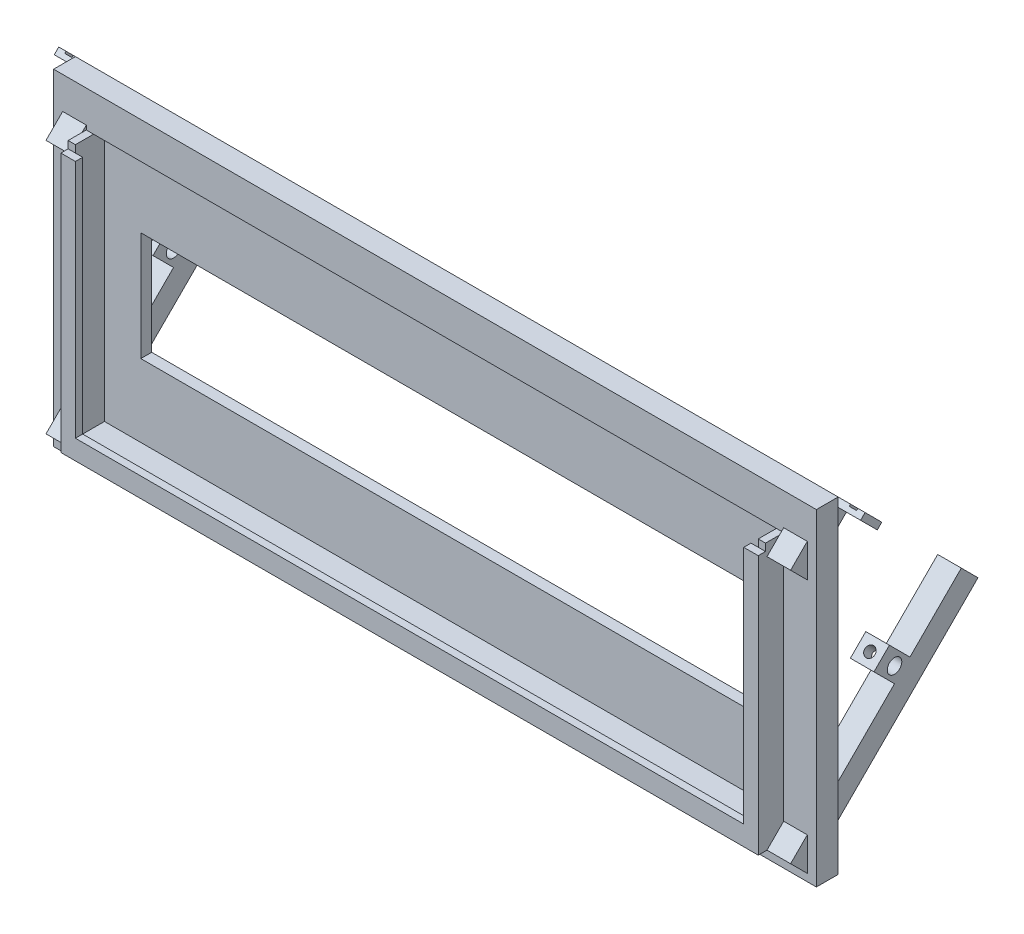
SolidWorks part; units mm, degrees
ref_plane "Front Plane" through (0, 0, 0) normal (0, 0, 1) x (1, 0, 0)
ref_plane "Top Plane" through (0, 0, 0) normal (0, 1, 0) x (1, 0, 0)
ref_plane "Right Plane" through (0, 0, 0) normal (1, 0, 0) x (0, 0, -1)
sketch "Sketch2" plane through (0, 0, 0) normal (0, 0, 1) x (1, 0, 0)
  line L1 (-105, 45) -> (105, 45)
  line L2 (-105, 45) -> (-105, -45)
  line L3 (-105, -45) -> (105, -45)
  line L4 (105, 45) -> (105, -45)
  line L5 (-105, 45) -> (105, -45) construction
  line L6 (-105, -45) -> (105, 45) construction
  point P0 (0, 0)
  dimension "D1" = 210
  dimension "D2" = 90
extrude "Boss-Extrude1" add sketch "Sketch2" along normal blind 6
sketch "Sketch3" plane through (0, 0, 6) normal (0, 0, 1) x (1, 0, 0)
  line L1 (-94, 35) -> (94, 35)
  line L2 (-94, 35) -> (-94, -35)
  line L3 (-94, -35) -> (94, -35)
  line L4 (94, 35) -> (94, -35)
  line L5 (-94, 35) -> (94, -35) construction
  line L6 (-94, -35) -> (94, 35) construction
  point P0 (0, 0)
  dimension "D1" = 70
  dimension "D2" = 188
extrude "Cut-Extrude1" cut sketch "Sketch3" against normal blind 3
sketch "Sketch4" plane through (0, 0, 3) normal (0, 0, 1) x (1, 0, 0)
  line L0 (94, -35) -> (94, 35) construction
  line L1 (-84, -15) -> (84, -15)
  line L2 (-84, -15) -> (-84, 15)
  line L3 (-84, 15) -> (84, 15)
  line L4 (84, -15) -> (84, 15)
  line L5 (-84, -15) -> (84, 15) construction
  line L6 (-84, 15) -> (84, -15) construction
  line L7 (-94, -35) -> (94, -35) construction
  point P0 (0, 0)
  dimension "D1" = 10
  dimension "D2" = 20
extrude "Cut-Extrude2" cut sketch "Sketch4" against normal up to next
sketch "Sketch7" plane through (-105, 0, 0) normal (-1, 0, 0) x (0, 0, 1)
  line L0 (-6.0104, 38.9896) -> (-1.4142, 43.5858)
  line L1 (-1.4142, 43.5858) -> (10.5962, 31.5754)
  line L2 (10.5962, 31.5754) -> (6, 26.9792)
  line L3 (-6.0104, 38.9896) -> (6, 26.9792)
  line L4 (6, 45) -> (6, -45) construction
  line L6 (0, 45) -> (-9.3025, 45) construction
  line L7 (0, 45) -> (-54.6388, -9.6388) construction
  line L8 (-41, 4) -> (6, -43)
  line L9 (6, -43) -> (10.5962, -38.4038)
  line L10 (10.5962, -38.4038) -> (-36.4038, 8.5962)
  line L11 (-36.4038, 8.5962) -> (-41, 4)
  line L12 (0, -45) -> (-15.811, -29.189) construction
  line L13 (0, 45) -> (0, -45) construction
  dimension "D1" = 45
  dimension "D2" = 6.5
  dimension "D3" = 2
  dimension "D4" = 45
  dimension "D5" = 6.5
  dimension "D6" = 2
  dimension "D7" = 45
  dimension "D8" = 45
extrude "Boss-Extrude2" add sketch "Sketch7" against normal blind 9
sketch "Sketch8" plane through (-105, 0, 0) normal (-1, 0, 0) x (0, 0, 1)
  line L0 (6, 36.1716) -> (10.5962, 31.5754)
  line L1 (10.5962, 31.5754) -> (6, 26.9792)
  line L2 (6, 26.9792) -> (6, 36.1716)
  line L3 (6, -33.8076) -> (6, -43)
  line L4 (6, -43) -> (10.5962, -38.4038)
  line L5 (10.5962, -38.4038) -> (6, -33.8076)
extrude "Cut-Extrude3" cut sketch "Sketch8" against normal blind 2.5
sketch "Sketch9" plane through (0, 10.4896, -10.4896) normal (0, -0.7071, 0.7071) x (1, 0, 0)
  line L6 (-96, 23.3198) -> (-102.5, 23.3198) construction
  line L7 (-102.5, 23.3198) -> (-102.5, 29.8198) construction
  circle A0 centre (-99.25, 26.5698) radius 3
  dimension "D1" = 6
  dimension "D3" = 3.25
  dimension "D2" = 3.25
extrude "Cut-Extrude5" cut sketch "Sketch9" against normal blind 7 contours A0 region at (-99.25, 29.2773, 8.2981)
sketch "Sketch11" plane through (-105, 0, 0) normal (-1, 0, 0) x (0, 0, 1)
  line L0 (-1.4142, 43.5858) -> (0, 42.1716)
  line L1 (0, 42.1716) -> (0, 32.9792)
  line L2 (0, 32.9792) -> (-6.0104, 38.9896)
  line L3 (-6.0104, 38.9896) -> (-1.4142, 43.5858)
  line L4 (-36.4038, 8.5962) -> (-41, 4)
  line L5 (-41, 4) -> (0, -37)
  line L6 (0, -37) -> (0, -27.8076)
  line L7 (0, -27.8076) -> (-36.4038, 8.5962)
extrude "Cut-Extrude7" cut sketch "Sketch11" against normal blind 2.5
sketch "Sketch14" plane through (0, 15.4393, -15.4393) normal (0, -0.7071, 0.7071) x (1, 0, 0)
  circle A0 centre (-99.25, 26.5698) radius 1.5
  dimension "D1" = 3
extrude "Cut-Extrude9" cut sketch "Sketch14" against normal up to next
sketch "Sketch15" plane through (0, -24.5, 24.5) normal (0, -0.7071, 0.7071) x (1, 0, 0)
  line L0 (-96, -19.663) -> (-96, -26.163) construction
  line L1 (-96, -26.163) -> (-102.5, -26.163) construction
  circle A0 centre (-99.25, -22.913) radius 3
  dimension "D1" = 6
  dimension "D2" = 3.25
  dimension "D3" = 3.25
extrude "Cut-Extrude10" cut sketch "Sketch15" against normal blind 7
sketch "Sketch17" plane through (0, -19.5503, 19.5503) normal (0, -0.7071, 0.7071) x (1, 0, 0)
  circle A0 centre (-99.25, -22.913) radius 1.5
  dimension "D1" = 3
extrude "Cut-Extrude12" cut sketch "Sketch17" against normal up to next
sketch "Sketch18" plane through (105, 0, 0) normal (1, 0, 0) x (0, 0, -1)
  line L0 (-10.5962, 31.5754) -> (1.4142, 43.5858)
  line L1 (1.4142, 43.5858) -> (6.0104, 38.9896)
  line L2 (6.0104, 38.9896) -> (-6, 26.9792)
  line L3 (-6, 26.9792) -> (-10.5962, 31.5754)
  line L4 (-10.5962, -38.4038) -> (36.4038, 8.5962)
  line L5 (36.4038, 8.5962) -> (41, 4)
  line L6 (41, 4) -> (-6, -43)
  line L7 (-6, -43) -> (-10.5962, -38.4038)
extrude "Boss-Extrude3" add sketch "Sketch18" against normal blind 9
sketch "Sketch19" plane through (0, 10.4896, -10.4896) normal (0, -0.7071, 0.7071) x (1, 0, 0)
  line L0 (96, 23.3198) -> (105, 23.3198) construction
  line L1 (96, 29.8198) -> (96, 23.3198) construction
  circle A0 centre (99.25, 26.5698) radius 3
  dimension "D1" = 6
  dimension "D3" = 3.25
  dimension "D2" = 3.25
extrude "Cut-Extrude13" cut sketch "Sketch19" against normal blind 7
sketch "Sketch20" plane through (0, -24.5, 24.5) normal (0, -0.7071, 0.7071) x (1, 0, 0)
  line L0 (96, -26.163) -> (105, -26.163) construction
  line L1 (96, -19.663) -> (96, -26.163) construction
  circle A0 centre (99.25, -22.913) radius 3
  dimension "D1" = 3.25
  dimension "D3" = 6
  dimension "D2" = 3.25
extrude "Cut-Extrude14" cut sketch "Sketch20" against normal blind 7
sketch "Sketch21" plane through (105, 0, 0) normal (1, 0, 0) x (0, 0, -1)
  line L0 (-10.5962, -38.4038) -> (-6, -33.8076)
  line L1 (-6, -33.8076) -> (-6, -43)
  line L2 (-6, -43) -> (-10.5962, -38.4038)
  line L3 (-6, 36.1716) -> (-6, 26.9792)
  line L4 (-6, 26.9792) -> (-10.5962, 31.5754)
  line L5 (-10.5962, 31.5754) -> (-6, 36.1716)
extrude "Cut-Extrude15" cut sketch "Sketch21" against normal blind 2.5
sketch "Sketch22" plane through (0, 15.4393, -15.4393) normal (0, -0.7071, 0.7071) x (1, 0, 0)
  circle A0 centre (99.25, 26.5698) radius 1.5
  dimension "D1" = 3
extrude "Cut-Extrude16" cut sketch "Sketch22" against normal up to next and the other way through all
sketch "Sketch23" plane through (0, -19.5503, 19.5503) normal (0, -0.7071, 0.7071) x (1, 0, 0)
  circle A0 centre (99.25, -22.913) radius 1.5
  dimension "D1" = 3
extrude "Cut-Extrude17" cut sketch "Sketch23" against normal up to next
sketch "Sketch24" plane through (105, 0, 0) normal (1, 0, 0) x (0, 0, -1)
  line L0 (1.4142, 43.5858) -> (0, 42.1716)
  line L1 (0, 42.1716) -> (0, 32.9792)
  line L2 (0, 32.9792) -> (6.0104, 38.9896)
  line L3 (6.0104, 38.9896) -> (1.4142, 43.5858)
  line L4 (0, -27.8076) -> (0, -37)
  line L5 (0, -37) -> (41, 4)
  line L6 (41, 4) -> (36.4038, 8.5962)
  line L7 (36.4038, 8.5962) -> (0, -27.8076)
extrude "Cut-Extrude18" cut sketch "Sketch24" against normal blind 2.5
sketch "Sketch25" plane through (0, -13.9038, -13.9038) normal (0, 0.7071, 0.7071) x (1, 0, 0)
  line L0 (-96, -19.663) -> (-96, 31.8198) construction
  line L1 (-96, 11.8198) -> (-102.5, 11.8198)
  line L2 (-96, 11.8198) -> (-96, 5.8198)
  line L3 (-96, 5.8198) -> (-102.5, 5.8198)
  line L4 (-102.5, 11.8198) -> (-102.5, 5.8198)
  line L5 (-102.5, -19.663) -> (-102.5, 31.8198) construction
  line L6 (-96, 31.8198) -> (-102.5, 31.8198) construction
  line L7 (102.5, 31.8198) -> (102.5, -19.663) construction
  line L8 (102.5, 11.8198) -> (96, 11.8198)
  line L9 (102.5, 11.8198) -> (102.5, 5.8198)
  line L10 (102.5, 5.8198) -> (96, 5.8198)
  line L11 (96, 11.8198) -> (96, 5.8198)
  line L12 (96, 31.8198) -> (96, -19.663) construction
  line L13 (96, 31.8198) -> (102.5, 31.8198) construction
  dimension "D1" = 20
  dimension "D2" = 6
  dimension "D3" = 6
  dimension "D4" = 20
extrude "Boss-Extrude4" add sketch "Sketch25" along normal blind 8
sketch "Sketch26" plane through (0, -8.247, -8.247) normal (0, 0.7071, 0.7071) x (1, 0, 0)
  line L0 (102.5, 11.8198) -> (96, 5.8198) construction
  line L1 (96, 11.8198) -> (102.5, 5.8198) construction
  line L2 (-96, 11.8198) -> (-102.5, 5.8198) construction
  line L4 (-102.5, 11.8198) -> (-96, 5.8198) construction
  circle A0 centre (99.25, 8.8198) radius 1.4
  circle A1 centre (-99.25, 8.8198) radius 1.4
  point P11 (99.25, 8.8198)
  point P19 (-99.25, 8.8198)
  dimension "D1" = 2.8
  dimension "D2" = 2.8
extrude "Cut-Extrude19" cut sketch "Sketch26" against normal blind 4
sketch "Sketch27" plane through (-102.5, 0, 0) normal (-1, 0, 0) x (0, 0, 1)
  line L0 (-12.3622, -4.1317) -> (-18.019, -9.7886) construction
  line L1 (10.5962, -38.4038) -> (-36.4038, 8.5962) construction
  circle A0 centre (-18.019, -5.5459) radius 2
  dimension "D1" = 4
  dimension "D2" = 3
  dimension "D3" = 3
extrude "Cut-Extrude20" cut sketch "Sketch27" against normal through all
sketch "Sketch28" plane through (102.5, 0, 0) normal (1, 0, 0) x (0, 0, -1)
  line L0 (1.4142, 43.5858) -> (6.0104, 38.9896)
  line L1 (6.0104, 38.9896) -> (4.773, 37.7522)
  line L2 (0, 32.9792) -> (6.0104, 38.9896) construction
  line L3 (4.773, 37.7522) -> (0.1768, 42.3483)
  line L5 (0.1768, 42.3483) -> (1.4142, 43.5858)
  dimension "D1" = 1.75
extrude "Boss-Extrude6" add sketch "Sketch28" along normal blind 8.5
sketch "Sketch29" plane through (0, 21.0858, 21.0858) normal (0, 0.7071, 0.7071) x (1, 0, 0)
  line L0 (96, 31.8198) -> (111, 31.8198) construction
  line L1 (107, 31.8198) -> (109, 31.8198)
  line L2 (107, 31.8198) -> (107, 31.3198)
  line L3 (107, 31.3198) -> (109, 31.3198)
  line L4 (109, 31.8198) -> (109, 31.3198)
  line L5 (111, 31.8198) -> (111, 30.0698) construction
  dimension "D1" = 0.5
  dimension "D2" = 2
  dimension "D3" = 2
extrude "Cut-Extrude21" cut sketch "Sketch29" against normal up to next
sketch "Sketch30" plane through (-102.5, 0, 0) normal (-1, 0, 0) x (0, 0, 1)
  line L0 (-1.4142, 43.5858) -> (-6.0104, 38.9896)
  line L1 (-6.0104, 38.9896) -> (-4.773, 37.7522)
  line L2 (-6.0104, 38.9896) -> (0, 32.9792) construction
  line L3 (-4.773, 37.7522) -> (-0.1768, 42.3483)
  line L4 (-0.1768, 42.3483) -> (-1.4142, 43.5858)
  dimension "D1" = 1.75
extrude "Boss-Extrude7" add sketch "Sketch30" along normal blind 8.5
sketch "Sketch31" plane through (0, 21.0858, 21.0858) normal (0, 0.7071, 0.7071) x (1, 0, 0)
  line L0 (-96, 31.8198) -> (-111, 31.8198) construction
  line L1 (-109, 31.8198) -> (-107, 31.8198)
  line L2 (-109, 31.8198) -> (-109, 31.3198)
  line L3 (-109, 31.3198) -> (-107, 31.3198)
  line L4 (-107, 31.8198) -> (-107, 31.3198)
  line L5 (-111, 30.0698) -> (-111, 31.8198) construction
  dimension "D1" = 0.5
  dimension "D2" = 2
  dimension "D3" = 2
extrude "Cut-Extrude22" cut sketch "Sketch31" against normal up to next
sketch "Sketch32" plane through (0, 0, 6) normal (0, 0, 1) x (1, 0, 0)
  line L0 (96, -33.8076) -> (96, -43) construction
  line L2 (-96, 38.4038) -> (-96, -38.4038) construction
  line L3 (-96, -38.4038) -> (96, -38.4038)
  line L4 (96, 38.4038) -> (96, -38.4038) construction
  line L5 (-96, 38.4038) -> (96, -38.4038) construction
  line L6 (-96, -38.4038) -> (96, 38.4038) construction
  line L7 (-94, 35) -> (-96, 35)
  line L9 (-94, 35) -> (-94, -35)
  line L10 (-94, -35) -> (94, -35)
  line L11 (94, 35) -> (94, -35)
  line L12 (-94, 35) -> (94, -35) construction
  line L13 (-94, -35) -> (94, 35) construction
  line L14 (94, 35) -> (96, 35)
  line L15 (-96, 35) -> (-96, -38.4038)
  line L16 (96, 35) -> (96, -38.4038)
  point P0 (0, 0)
  point P8 (0, 0)
extrude "Boss-Extrude8" add sketch "Sketch32" along normal blind 5
sketch "Sketch33" plane through (0, 0, 11) normal (0, 0, 1) x (1, 0, 0)
  line L0 (94, 35) -> (94, -35) construction
  line L2 (-96, 38.4038) -> (-96, -38.4038) construction
  line L3 (-96, -38.4038) -> (96, -38.4038)
  line L4 (96, 38.4038) -> (96, -38.4038) construction
  line L5 (-96, 38.4038) -> (96, -38.4038) construction
  line L6 (-96, -38.4038) -> (96, 38.4038) construction
  line L8 (-92, 33) -> (-92, -33)
  line L9 (-92, -33) -> (92, -33)
  line L10 (92, 33) -> (92, -33)
  line L11 (-92, 33) -> (92, -33) construction
  line L12 (-92, -33) -> (92, 33) construction
  line L13 (94, -35) -> (-94, -35) construction
  line L14 (92, 33) -> (96, 33)
  line L15 (-92, 33) -> (-96, 33)
  line L16 (96, 33) -> (96, -38.4038)
  line L17 (-96, 33) -> (-96, -38.4038)
  point P0 (0, 0)
  point P7 (0, 0)
  dimension "D1" = 2
  dimension "D2" = 2
extrude "Boss-Extrude9" add sketch "Sketch33" along normal blind 2
